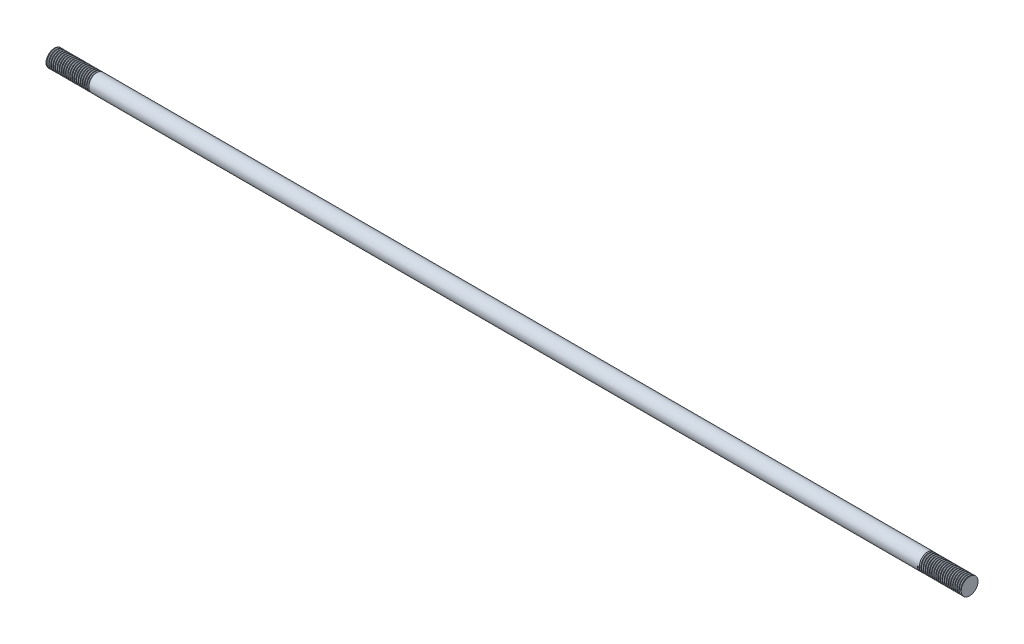
SolidWorks part; units mm, degrees
ref_plane "Front Plane" through (0, 0, 0) normal (0, 0, 1) x (1, 0, 0)
ref_plane "Top Plane" through (0, 0, 0) normal (0, 1, 0) x (1, 0, 0)
ref_plane "Right Plane" through (0, 0, 0) normal (1, 0, 0) x (0, 0, -1)
sketch "Sketch1" plane through (0, 0, 0) normal (1, 0, 0) x (0, 0, -1)
  circle A0 centre (0, 0) radius 8
  dimension "D1" = 16
extrude "Boss-Extrude1" add sketch "Sketch1" along normal mid plane 870
thread "Thread1" pitch 2 method cut profile "Thread Profile1" start angle 0, offset 0, length 40, pitch 2, diameter 16
ref_plane "Plane1" through (435, 0, 8) normal (0, -1, 0) x (0, 0, 1)
sketch "Thread Profile1" plane through (435, 0, 8) normal (0, -1, 0) x (0, 0, 1)
  line L0 (0, 0) -> (0, 2) construction
  line L11 (0, 0) -> (0, 1.75)
  line L12 (0, 1.75) -> (-1.0825, 1.125)
  line L13 (-1.0825, 1.125) -> (-1.0825, 0.625)
  line L15 (-1.0825, 0.625) -> (0, 0)
  line L17 (-1.0825, 0.875) -> (0, 0.875) construction
  point P2 (0, 0)
  dimension "Pitch" = 2
  dimension "Profile_Angle" = 60
  dimension "Profile_Land" = 0.5
  dimension "Profile_Height" = 1.0825
thread "Thread2" pitch 2 method cut profile "Thread Profile2" start angle 0, offset 0, length 40, pitch 2, diameter 16
ref_plane "Plane2" through (-435, 0, -8) normal (0, -1, 0) x (0, 0, -1)
sketch "Thread Profile2" plane through (-435, 0, -8) normal (0, -1, 0) x (0, 0, -1)
  line L0 (0, 0) -> (0, 2) construction
  line L11 (0, 0) -> (0, 1.75)
  line L12 (0, 1.75) -> (-1.0825, 1.125)
  line L13 (-1.0825, 1.125) -> (-1.0825, 0.625)
  line L15 (-1.0825, 0.625) -> (0, 0)
  line L17 (-1.0825, 0.875) -> (0, 0.875) construction
  point P2 (0, 0)
  dimension "Pitch" = 2
  dimension "Profile_Angle" = 60
  dimension "Profile_Land" = 0.5
  dimension "Profile_Height" = 1.0825
